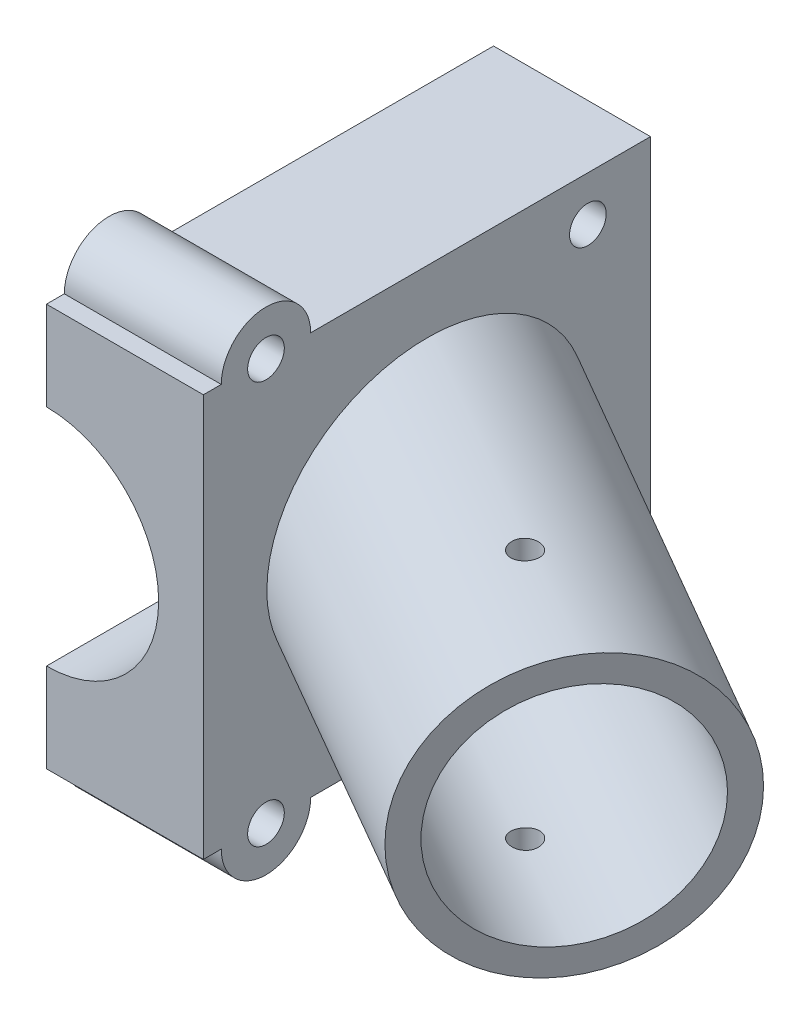
SolidWorks part; units mm, degrees
material "PLA"
ref_plane "Front Plane" through (0, 0, 0) normal (0, 0, 1) x (1, 0, 0)
ref_plane "Top Plane" through (0, 0, 0) normal (0, 1, 0) x (1, 0, 0)
ref_plane "Right Plane" through (0, 0, 0) normal (1, 0, 0) x (0, 0, -1)
sketch "Sketch1" plane through (0, 0, 0) normal (0, 0, 1) x (1, 0, 0)
  line L0 (-17.55, 22.5) -> (-17.55, 0)
  line L1 (55, 0) -> (-55, 0) construction
  line L2 (-17.55, 0) -> (17.55, 0)
  line L3 (17.55, 0) -> (17.55, 22.5)
  line L4 (-17.55, 22.5) -> (-12.55, 22.5)
  line L5 (17.55, 22.5) -> (12.55, 22.5)
  line L6 (0, -44.7868) -> (0, 44.7868) construction
  arc A0 (-12.55, 22.5) -> (12.55, 22.5) centre (0, 22.5) ccw
  dimension "D1" = 12.55
  dimension "D2" = 22.5
  dimension "D3" = 5
extrude "Boss-Extrude1" add sketch "Sketch1" along normal mid plane 50
sketch "Construct1" plane through (0, 0, 0) normal (0, 1, 0) x (1, 0, 0)
  line L0 (17.55, 0) -> (43.5308, -15) construction
  line L1 (-44.2539, 0) -> (44.2539, 0) construction
  line L2 (34.7676, -0.1782) -> (26.3131, -14.8218) construction
  line L3 (17.55, -25) -> (17.55, 25) construction
  point P6 (30.5404, -7.5)
  point P7 (30.5404, -7.5)
  dimension "D1" = 30
  dimension "D2" = 15
ref_plane "LegBuildPlane" through (26.1529, 0, 15.0994) normal (0.866, 0, 0.5) x (0.5, 0, -0.866)
sketch "Sketch5" plane through (26.1529, 0, 15.0994) normal (0.866, 0, 0.5) x (0.5, 0, -0.866)
  line L0 (-6.725, 22.5) -> (-3.775, 22.5)
  line L1 (21.325, 22.5) -> (24.275, 22.5)
  line L2 (17.2295, 0) -> (0.3205, 0) construction
  arc A0 (-3.775, 22.5) -> (21.325, 22.5) centre (8.775, 22.5) ccw
  arc A1 (-6.725, 22.5) -> (24.275, 22.5) centre (8.775, 22.5) ccw
  point P9 (8.775, 0)
  dimension "D1" = 15.5
  dimension "D2" = 12.55
  dimension "D3" = 22.5
  dimension "D4" = 0
extrude "Boss-Extrude2" add sketch "Sketch5" against normal up to surface and the other way blind 30 up to face at (17.55, 11.25, 0)
sketch "Sketch9" plane through (-17.55, 0, 0) normal (-1, 0, 0) x (0, 0, 1)
  line L2 (55, 0) -> (-55, 0) construction
  line L3 (-25, 22.5) -> (-25, 0) construction
  circle A0 centre (-18, 5) radius 2.05
  dimension "D3" = 5
  dimension "D1" = 4.1
  dimension "D4" = 7
extrude "Cut-Extrude3" cut sketch "Sketch9" against normal up to surface (35.1 mm away) up to face at (17.55, 12.4167, 0)
sketch "Construct2" plane through (0, 22.5, 0) normal (0, 1, 0) x (1, 0, 0)
  line L0 (20.1481, -15.9915) -> (32.6981, 5.7457) construction
  line L2 (50.2461, -33.3686) -> (17.55, -14.4915) construction
  line L3 (62.7961, -11.6314) -> (17.55, 14.4915) construction
  line L4 (17.55, 0) -> (26.4231, -5.1229) construction
  line L11 (-44.2539, 0) -> (44.2539, 0) construction
  dimension "D1" = 3
  dimension "D2" = 90
ref_plane "LegBuildPlane2" through (22.0356, 0, 12.7222) normal (0.866, 0, 0.5) x (0.5, 0, -0.866)
sketch "Sketch12" plane through (22.0356, 0, 12.7222) normal (0.866, 0, 0.5) x (0.5, 0, -0.866)
  line L0 (-3.775, 22.5) -> (21.325, 22.5)
  arc A0 (-3.775, 22.5) -> (21.325, 22.5) centre (8.775, 22.5) ccw
extrude "Boss-Extrude5" add sketch "Sketch12" against normal up to surface (17.4915 mm away) up to face at (17.55, 16.225, 0)
mirror "Mirror1" about plane through (17.55, 22.5, 25) normal (0, -1, 0) of "Boss-Extrude2", "Boss-Extrude1", "Cut-Extrude3", "Boss-Extrude5"
sketch "Sketch13" plane through (0, 0, 0) normal (0, 1, 0) x (1, 0, 0)
  line L0 (17.55, 0) -> (43.5308, -15) construction
  line L1 (48.7711, -35.9234) -> (64.2711, -9.0766) construction
  circle A0 centre (43.5308, -15) radius 1.55
  dimension "D2" = 3.1
  dimension "D1" = 15
extrude "Cut-Extrude4" cut sketch "Sketch13" along normal through all
sketch "Sketch16" plane through (0, 0, 0) normal (1, 0, 0) x (0, 0, -1)
  line L0 (55, 0) -> (-55, 0) construction
  line L1 (25, 45) -> (-25, 45)
  line L2 (25, 45) -> (25, 0)
  line L3 (25, 0) -> (-25, 0)
  line L4 (-25, 45) -> (-25, 0)
  line L5 (-25, 45) -> (-25, 0) construction
extrude "Cut-Extrude5" cut sketch "Sketch16" against normal up to surface (17.55 mm away) up to face at (-17.55, 40, -15.95)
sketch "Sketch18" plane through (0, 0, 0) normal (-1, 0, 0) x (0, 0, 1)
  line L0 (55, 0) -> (-55, 0) construction
  line L2 (13, 0) -> (23, 0)
  arc A0 (23, 0) -> (13, 0) centre (18, 0) cw
  circle A3 centre (-18, 5) radius 2.05 construction
  dimension "D3" = 5
  dimension "D1" = 36
extrude "Boss-Extrude6" add sketch "Sketch18" against normal blind 17.55
sketch "Sketch20" plane through (0, 0, 0) normal (-1, 0, 0) x (0, 0, 1)
  circle A0 centre (18, 0) radius 2.05
  dimension "D1" = 4.1
extrude "Cut-Extrude6" cut sketch "Sketch20" against normal up to surface (17.55 mm away) up to face at (17.55, 37.95, -18)
ref_plane "HolePlane" through (0, 22.5, 0) normal (0, 1, 0) x (1, 0, 0)
mirror "Mirror2" about plane through (0, 22.5, 0) normal (0, 1, 0) of "Boss-Extrude6", "Cut-Extrude6"
equation "\"TubeDiam\"= 12.55"
equation "\"D1@Sketch1\"=\"TubeDiam\""
equation "\"D2@Sketch1\"=\"ClampHeight\""
equation "\"MountLength\"= 50"
equation "\"D1@Boss-Extrude1\"=\"MountLength\""
equation "\"MountHoleSize\"=3.1"
equation "\"LipWidth\"= 5"
equation "\"D3@Sketch1\"=\"LipWidth\""
equation "\"LegDiam\"=12.55"
equation "\"LegThickness\"= \"TubeDiam\" + 2.95"
equation "\"D1@Sketch5\"=\"LegThickness\""
equation "\"D2@Sketch5\"=\"TubeDiam\""
equation "\"ClampHeight\"= \"TubeDiam\" + 9.95"
equation "\"D3@Sketch5\"=\"ClampHeight\""
equation "\"HubHoleDist\"=7"
equation "\"HubHoleSize\"=4.1"
equation "\"D2@Sketch13\"=\"MountHoleSize\""
equation "\"D1@Sketch9\"=\"HubHoleSize\""
equation "\"D4@Sketch9\"=\"HubHoleDist\""
equation "\"D1@Sketch18\"=\"MountLength\" - 2 * \"HubHoleDist\""
equation "\"D1@Boss-Extrude6\"=\"TubeDiam\" +5"
equation "\"D1@Sketch20\"=\"HubHoleSize\""
